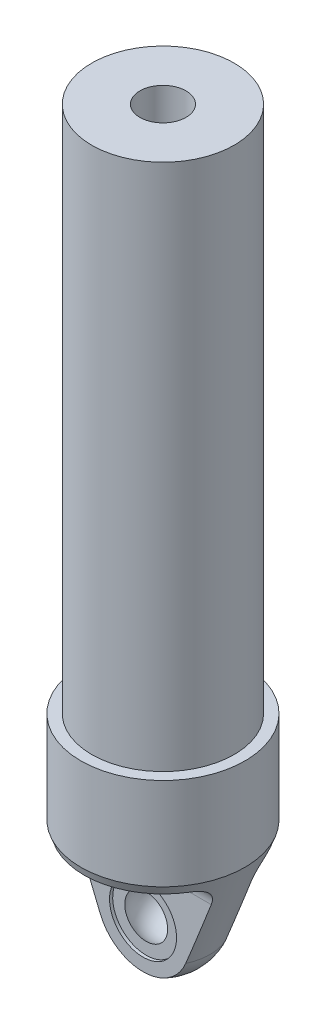
SolidWorks part; units mm, degrees
ref_plane "Front Plane" through (0, 0, 0) normal (0, 0, 1) x (1, 0, 0)
ref_plane "Top Plane" through (0, 0, 0) normal (0, 1, 0) x (1, 0, 0)
ref_plane "Right Plane" through (0, 0, 0) normal (1, 0, 0) x (0, 0, -1)
sketch "Sketch1" plane through (0, 0, 0) normal (0, 0, 1) x (1, 0, 0)
  line L0 (0, 0) -> (0, 166) construction
  line L1 (0, 166) -> (-17, 166)
  line L2 (-17, 166) -> (-17, 40)
  line L3 (-17, 40) -> (-19.6, 40)
  line L4 (-19.6, 40) -> (-19.6, 18)
  line L5 (-19.6, 18) -> (-11.2303, -4.2285)
  line L6 (0, 0) -> (0, -12) construction
  line L7 (0, 166) -> (0, -12)
  arc A0 (-11.2303, -4.2285) -> (0, -12) centre (0, 0) ccw
  dimension "D4" = 24
  dimension "D1" = 126
  dimension "D2" = 17
  dimension "D3" = 2.6
  dimension "D5" = 18
  dimension "D6" = 22
revolve "Revolve1" add sketch "Sketch1" angle 360 about L7
sketch "Sketch2" plane through (0, 0, 0) normal (1, 0, 0) x (0, 0, -1)
  line L0 (0, 0) -> (0, 166) construction
  line L1 (17, 166) -> (-17, 166) construction
  line L3 (-4.75, -11.5482) -> (-4.75, 11)
  line L4 (-9.75, 16) -> (-25.8703, 16)
  line L5 (-25.8703, 16) -> (-25.8703, -11.5482)
  line L6 (-25.8703, -11.5482) -> (-4.75, -11.5482)
  line L7 (-19.6, 18) -> (19.6, 18) construction
  line L8 (25.8703, 16) -> (25.8703, -11.5482)
  line L9 (25.8703, -11.5482) -> (4.75, -11.5482)
  line L10 (4.75, -11.5482) -> (4.75, 11)
  line L11 (9.75, 16) -> (25.8703, 16)
  arc A0 (-4.75, 11) -> (-9.75, 16) centre (-9.75, 11) ccw
  arc A1 (4.75, 11) -> (9.75, 16) centre (9.75, 11) cw
  dimension "D3" = 5
  dimension "D1" = 4.75
  dimension "D2" = 2
extrude "Cut-Extrude1" cut sketch "Sketch2" against normal mid plane 50
sketch "Sketch3" plane through (0, 0, 0) normal (0, 0, 1) x (1, 0, 0)
  line L0 (0, -12) -> (0, 19.3658) construction
  line L1 (0, -6.5) -> (0, 6.5)
  arc A0 (-11.2303, -4.2285) -> (11.2303, -4.2285) centre (0, 0) ccw construction
  arc A1 (0, 6.5) -> (0, -6.5) centre (0, 0) ccw
  dimension "D1" = 13
revolve "Cut-Revolve1" cut sketch "Sketch3" angle 360 about L0
sketch "Sketch4" plane through (0, 0, 0) normal (0, 0, 1) x (1, 0, 0)
  circle A0 centre (0, 0) radius 8
  dimension "D1" = 16
extrude "Cut-Extrude2" cut sketch "Sketch4" against normal blind 4 from offset 4 offset against normal yes
extrude "Cut-Extrude3" cut sketch "Sketch4<2>" along normal blind 4 from offset 4
sketch "Sketch4<2>" plane through (0, 0, 0) normal (0, 0, 1) x (1, 0, 0) same geometry as "Sketch4"
sketch "Sketch5" plane through (0, 166, 0) normal (0, 1, 0) x (1, 0, 0)
  circle A0 centre (0, 0) radius 5.5
  dimension "D1" = 11
extrude "Cut-Extrude4" cut sketch "Sketch5" against normal blind 120
